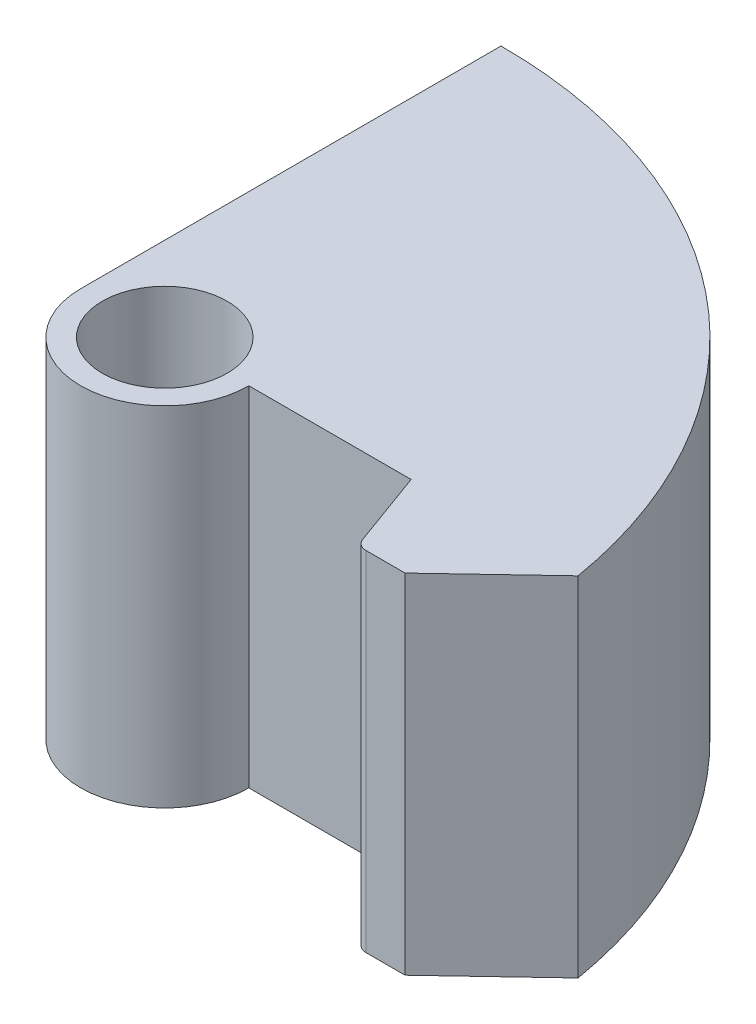
SolidWorks part; units mm, degrees
ref_plane "Front Plane" through (0, 0, 0) normal (0, 0, 1) x (1, 0, 0)
ref_plane "Top Plane" through (0, 0, 0) normal (0, 1, 0) x (1, 0, 0)
ref_plane "Right Plane" through (0, 0, 0) normal (1, 0, 0) x (0, 0, -1)
sketch "Sketch2" plane through (0, 0, 0) normal (0, 1, 0) x (1, 0, 0)
  line L0 (-3.5, 0) -> (-3.5, -3.5)
  line L1 (-3.5, -3.5) -> (0, -3.5)
  line L2 (-3.5, -3.5) -> (17.5, -3.5)
  line L3 (-3.5, -3.5) -> (-3.5, 17.5)
  line L4 (3.5, 0) -> (17.2063, 0)
  circle A0 centre (0, 0) radius 2.6
  circle A1 centre (0, 0) radius 3.5
  circle A2 centre (-3.5, -3.5) radius 21
  dimension "D1" = 5.2
  dimension "D2" = 7
  dimension "D4" = 42
  dimension "D3" = 3.5
extrude "Boss-Extrude1" add sketch "Sketch2" along normal blind 14.6 contours L4 A2 L3 A1 | A1 A0 region at (5.3795, 0, -7.7748) region at (0, 0, -3.401)
sketch "Sketch4" plane through (0, 14.6, 0) normal (0, 1, 0) x (1, 0, 0)
  line L1 (-8.6615, 22.387) -> (30.5932, 22.387)
  line L2 (-8.6615, 22.387) -> (-8.6615, -12.7916)
  line L3 (-8.6615, -12.7916) -> (30.5932, -12.7916)
  line L4 (30.5932, 22.387) -> (30.5932, -12.7916)
extrude "Cut-Extrude1" cut sketch "Sketch4" against normal blind 0.1
sketch "Sketch7" plane through (0, 0, 0) normal (0, -1, 0) x (-1, 0, 0)
  line L1 (-3.5, 0) -> (-17.2063, 0) construction
  line L2 (-11.4112, -3.171) -> (-10.257, 0)
  line L3 (-10.257, 0) -> (-13.505, 0)
  line L4 (-13.505, 0) -> (-17.2063, 0)
  line L5 (-11.881, -3.5) -> (-13.505, -3.5)
  line L7 (-17.2063, 0) -> (-13.505, -3.5)
  arc A0 (-11.4112, -3.171) -> (-11.881, -3.5) centre (-11.881, -3) cw
  arc A1 (3.5, 17.5) -> (-17.2063, 0) centre (3.5, -3.5) ccw construction
  line M5 (-17.2063, 0) -> (-3.5, 0)
  dimension "D1" = 0.5
  dimension "D2" = 3
  dimension "D3" = 70
extrude "Boss-Extrude5" add sketch "Sketch7" against normal up to surface (14.5 mm away) contours A0 L2 M5 region at (13.24, 0, 1.4219) up to face at (0, 14.5, 2.6)
